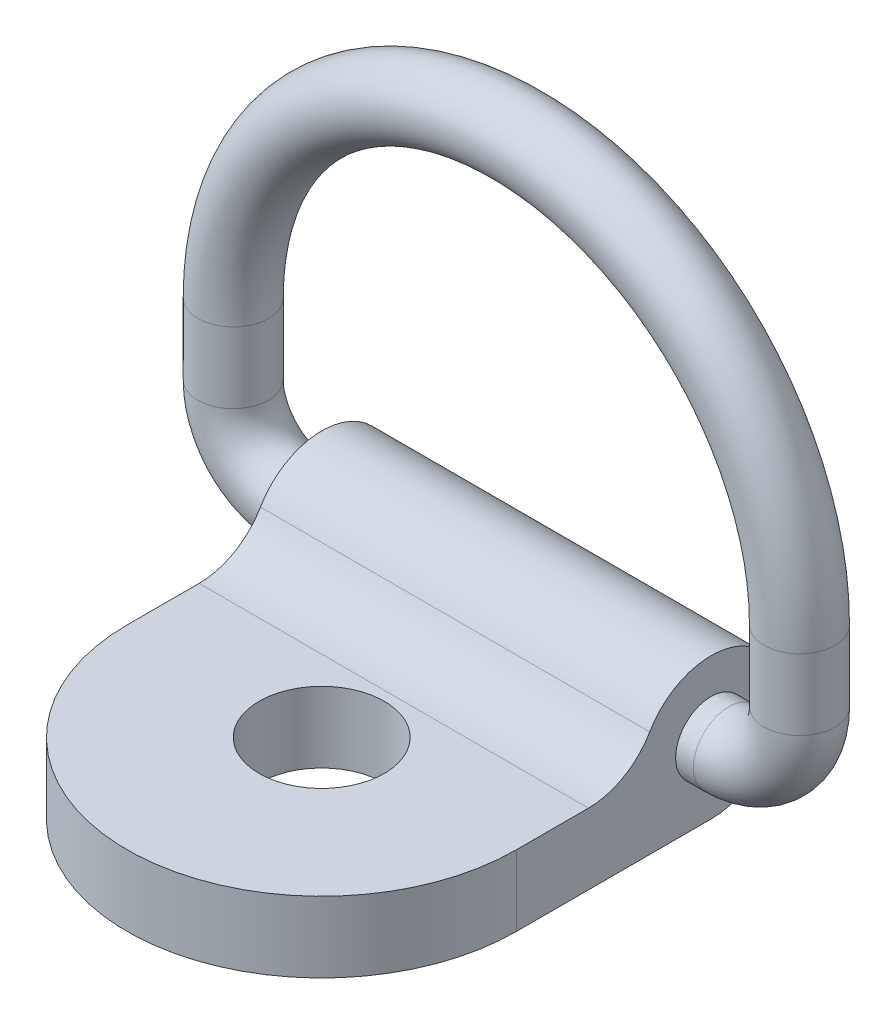
SolidWorks part; units mm, degrees
material "AISI 316 Annealed Stainless Steel Bar (SS)"
ref_plane "Front Plane" through (0, 0, 0) normal (0, 0, 1) x (1, 0, 0)
ref_plane "Top Plane" through (0, 0, 0) normal (0, 1, 0) x (1, 0, 0)
ref_plane "Right Plane" through (0, 0, 0) normal (1, 0, 0) x (0, 0, -1)
sketch "Sketch2" plane through (0, 0, 0) normal (0, 0, 1) x (1, 0, 0)
  line L0 (0, 0) -> (0, 19.05) construction
  line L1 (-9.525, 0) -> (9.525, 0)
  line L2 (12.7, 3.175) -> (12.7, 6.35)
  line L3 (-12.7, 3.175) -> (-12.7, 6.35)
  arc A0 (-12.7, 6.35) -> (12.7, 6.35) centre (0, 6.35) cw
  arc A1 (9.525, 0) -> (12.7, 3.175) centre (9.525, 3.175) ccw
  arc A2 (-9.525, 0) -> (-12.7, 3.175) centre (-9.525, 3.175) cw
  dimension "D3" = 3.175
  dimension "D1" = 19.05
  dimension "D2" = 25.4
sketch "Sketch3" plane through (0, 0, 0) normal (1, 0, 0) x (0, 0, -1)
  circle A0 centre (0, 0) radius 1.5875
  dimension "D1" = 3.175
sweep "Sweep1" add profiles "Sketch3" path "Sketch2"
sketch "Sketch4" plane through (0, 0, 0) normal (1, 0, 0) x (0, 0, -1)
  line L0 (-17.4625, -3.175) -> (0, -3.175)
  line L1 (-17.4625, -3.175) -> (-17.4625, 0)
  line L2 (-17.4625, 0) -> (-5.4993, 0)
  circle A0 centre (0, 0) radius 1.5875
  arc A1 (0, -3.175) -> (-2.7496, 1.5875) centre (0, 0) ccw
  arc A2 (-2.7496, 1.5875) -> (-5.4993, 0) centre (-5.4993, 3.175) cw
  point P9 (3.175, 0)
  dimension "D1" = 3.175
  dimension "D2" = 3.175
  dimension "D5" = 3.175
  dimension "D3" = 20.6375
  dimension "D4" = 3.175
extrude "Boss-Extrude1" add sketch "Sketch4" along normal mid plane 17.4625
fillet "Fillet1" 2 edges at (-8.7312, -1.5875, 17.4625) (8.7312, -1.5875, 17.4625) type full round first side face at (-8.7312, -0.5499, 7.7674) second side face at (8.7312, -0.5499, 7.7674) middle face at (0, -1.5875, 17.4625)
hole_wizard "#2 (0.221) Diameter Hole1" positions "Sketch6" profile "Sketch5" hole size "#2" standard "ANSI Inch" end condition through all
sketch "Sketch6" plane through (0, 0, 0) normal (0, 1, 0) x (1, 0, 0)
  line L0 (0, 0) -> (0, -8.7313) construction
  arc A0 (-8.7312, -8.7313) -> (8.7312, -8.7313) centre (0, -8.7313) ccw construction
  point P0 (0, -8.7313)
sketch "Sketch5" plane through (0, 0, 8.7313) normal (1, 0, 0) x (0, 0, 1)
  line L0 (0, 0) -> (0, 3.175)
  line L1 (0, 3.175) -> (2.8067, 3.175)
  line L2 (2.8067, 3.175) -> (2.8067, 0)
  line L5 (2.8067, 0) -> (0, 0)
  line L11 (0, -6.35) -> (0, 107.95) construction
  dimension "Thru Hole Dia." = 5.6134
  dimension "Thru Hole Depth" = 3.175
